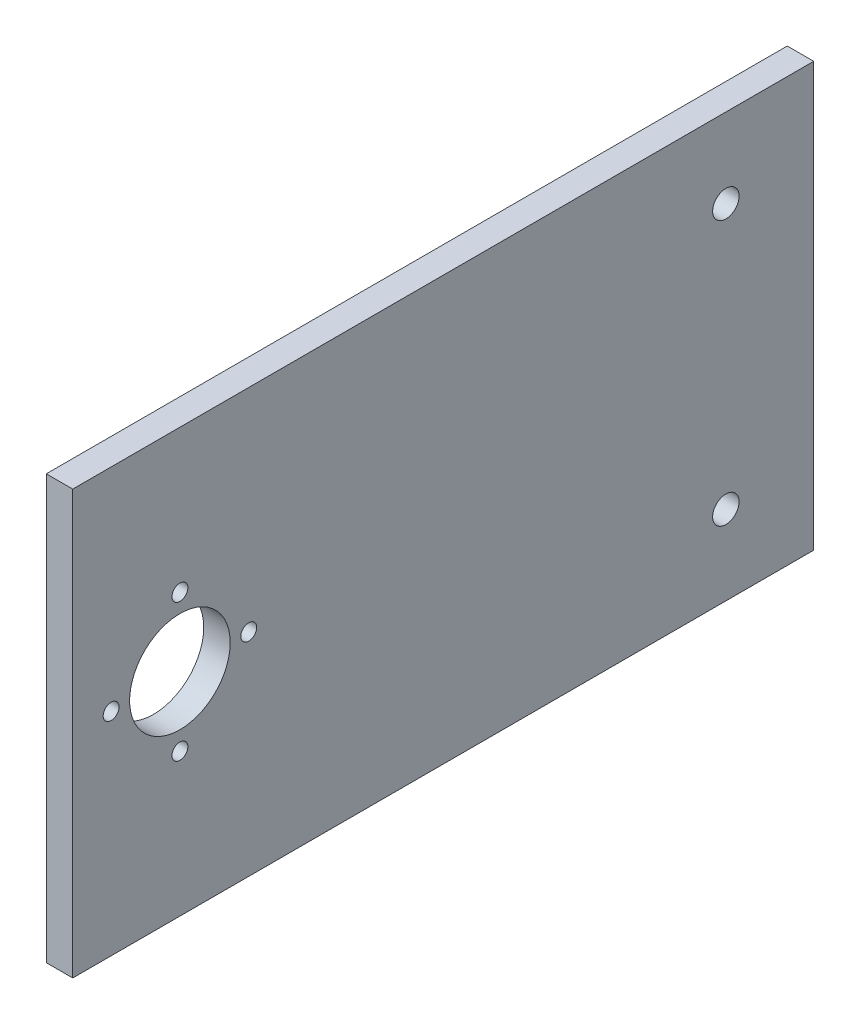
SolidWorks part; units mm, degrees
ref_plane "Front Plane" through (0, 0, 0) normal (1, 0, 0) x (0, 1, 0)
ref_plane "Top Plane" through (0, 0, 0) normal (0, 0, 1) x (0, 1, 0)
ref_plane "Right Plane" through (0, 0, 0) normal (0, 1, 0) x (-1, 0, 0)
sketch "Sketch1" plane through (0, 0, 0) normal (1, 0, 0) x (0, 1, 0)
  line L0 (0, 70) -> (0, -70) construction
  line L1 (-40, -70) -> (40, -70)
  line L2 (-40, -70) -> (-40, 70)
  line L3 (-40, 70) -> (40, 70)
  line L4 (40, -70) -> (40, 70)
  line L5 (-40, -70) -> (40, 70) construction
  line L6 (-40, 70) -> (40, -70) construction
  line L7 (-40, 49.75) -> (40, 49.75) construction
  line L9 (-25, -53.4) -> (25, -53.4) construction
  line L10 (-25, -53.4) -> (-25, 53.4) construction
  line L11 (-25, 53.4) -> (25, 53.4) construction
  line L12 (25, -53.4) -> (25, 53.4) construction
  line L13 (-25, -53.4) -> (25, 53.4) construction
  line L14 (-25, 53.4) -> (25, -53.4) construction
  circle A1 centre (0, 62.75) radius 1.5
  circle A2 centre (0, 36.75) radius 1.5
  circle A3 centre (-13, 49.75) radius 1.5
  circle A4 centre (13, 49.75) radius 1.5
  circle A5 centre (0, 49.75) radius 9.5
  circle A6 centre (-25, -53.4) radius 2.5
  circle A7 centre (25, -53.4) radius 2.5
  point P0 (0, 0)
  point P20 (0, 0)
  dimension "D5" = 3
  dimension "D6" = 3
  dimension "D7" = 13
  dimension "D8" = 19
  dimension "D11" = 5
  dimension "D12" = 5
  dimension "D1" = 80
  dimension "D2" = 140
  dimension "D3" = 119.75
  dimension "D4" = 13
  dimension "D9" = 16.6
  dimension "D10" = 50
extrude "Boss-Extrude1" add sketch "Sketch1" along normal blind 5
